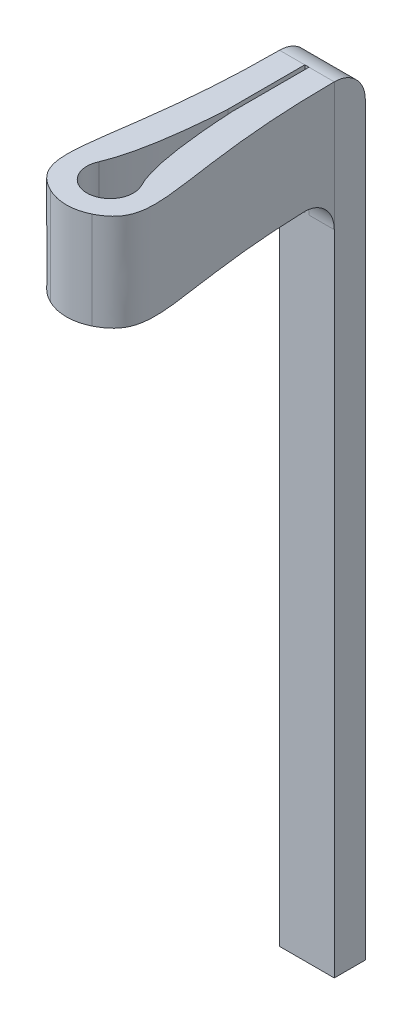
SolidWorks part; units mm, degrees
ref_plane "Front Plane" through (0, 0, 0) normal (0, 0, 1) x (1, 0, 0)
ref_plane "Top Plane" through (0, 0, 0) normal (0, 1, 0) x (1, 0, 0)
ref_plane "Right Plane" through (0, 0, 0) normal (1, 0, 0) x (0, 0, -1)
sketch "Sketch1" plane through (0, 0, 0) normal (0, 1, 0) x (1, 0, 0)
  line L0 (0, 0) -> (0, 6.2146) construction
  line L1 (-0.6908, 2.6065) -> (-0.2172, 3.7387) construction
  line L2 (-0.0683, 8.724) -> (0.0683, 8.724)
  line L3 (-0.0683, 8.724) -> (-0.0683, 6.2146)
  line L5 (0.0683, 8.724) -> (0.0683, 6.2146)
  line L6 (-0.2172, 3.7387) -> (-0.0683, 6.2146) construction
  line L9 (0.6908, 2.6065) -> (0.2181, 3.4821) construction
  line L10 (0.2181, 3.4821) -> (0.0683, 6.2146) construction
  line L11 (-0.8958, 8.724) -> (-0.8958, 4.5422) construction
  line L12 (-0.8958, 4.5422) -> (-1.5887, 2.2193) construction
  line L20 (-1.5887, 2.2193) -> (-2.0882, 1.3377) construction
  line L21 (-2.0882, 1.3377) -> (0, 0.7662) construction
  line L22 (0.8958, 8.724) -> (0.8958, 4.5422) construction
  line L23 (0.8958, 4.5422) -> (1.5887, 2.2193) construction
  line L25 (1.5887, 2.2193) -> (2.0882, 1.3377) construction
  line L26 (2.0882, 1.3377) -> (0, 0.7662) construction
  line L27 (-0.8958, 8.724) -> (0, 8.724)
  line L28 (0.8958, 8.724) -> (0, 8.724)
  arc A0 (-0.6908, 2.6065) -> (0.6908, 2.6065) centre (0, 2.2849) ccw
  spline S3 degree 2 poles (0.6908, 2.6065) (0.2181, 3.4821) (0.0683, 6.2146) knots 0 0 0 1 1 1
  spline S4 degree 2 poles (-0.6908, 2.6065) (-0.2172, 3.7387) (-0.0683, 6.2146) knots 0 0 0 1 1 1
  spline S5 degree 4 poles (-0.8958, 8.724) (-0.8958, 4.5422) (-1.5887, 2.2193) (-2.0882, 1.3377) (0, 0.7662) knots 0 0 0 0 0 1 1 1 1 1
  spline S6 degree 4 poles (0.8958, 8.724) (0.8958, 4.5422) (1.5887, 2.2193) (2.0882, 1.3377) (0, 0.7662) knots 0 0 0 0 0 1 1 1 1 1
  point P8 (-0.508, -2.5134)
  point P18 (0.508, -2.5134)
  point P21 (0, -2.54)
  dimension "D1" = 1.524
extrude "Boss-Extrude1" add sketch "Sketch1" along normal blind 1.5875 and the other way blind 1.5875 contours S6 L28 L5 S3 A0 S4 L3 L27 S5 region at (-0.1529, 0, -7.4693)
ref_axis "Axis1" through (0, 0, -2.032) along (0, 0, 1)
ref_plane "Plane1" through (0, 0, 2.54) normal (0, 0, 1) x (1, 0, 0)
ref_axis "Axis2" through (0, 1.7463, 2.54) along (0, -1, 0)
fillet "Fillet1" radius 1.524 1 edges at (0, 0, -0.7662)
ref_plane "Plane2" through (0, 0, -2.6065) normal (0, 0, -1) x (-1, 0, 0)
ref_plane "Plane3" through (0, 0, -3.1145) normal (0, 0, -1) x (-1, 0, 0)
sketch "Sketch2" plane through (0, 0, 0) normal (1, 0, 0) x (0, 0, -1)
  line L0 (8.724, -1.5875) -> (8.724, 1.5875) construction
  line L1 (8.724, -1.5875) -> (8.724, 1.5875)
  line L3 (8.724, 1.5875) -> (9.74, 1.5875)
  line L4 (8.724, 1.5875) -> (8.724, -23.8125)
  line L5 (8.724, -23.8125) -> (9.74, -23.8125)
  line L6 (9.74, 1.5875) -> (9.74, -23.8125)
  dimension "D1" = 1.016
  dimension "D2" = 25.4
extrude "Boss-Extrude2" add sketch "Sketch2" along normal up to vertex (0.8958 mm away) and the other way up to vertex (0.8958 mm away) contours L6 L3 L1 L4 L5 region at (0, -11.1125, -9.232) up to point (0.8958, 1.5875, -8.724) other way up to point (-0.8958, 1.5875, -8.724)
fillet "Fillet2" radius 1.016 3 edges at (0, 1.5875, -9.74)
